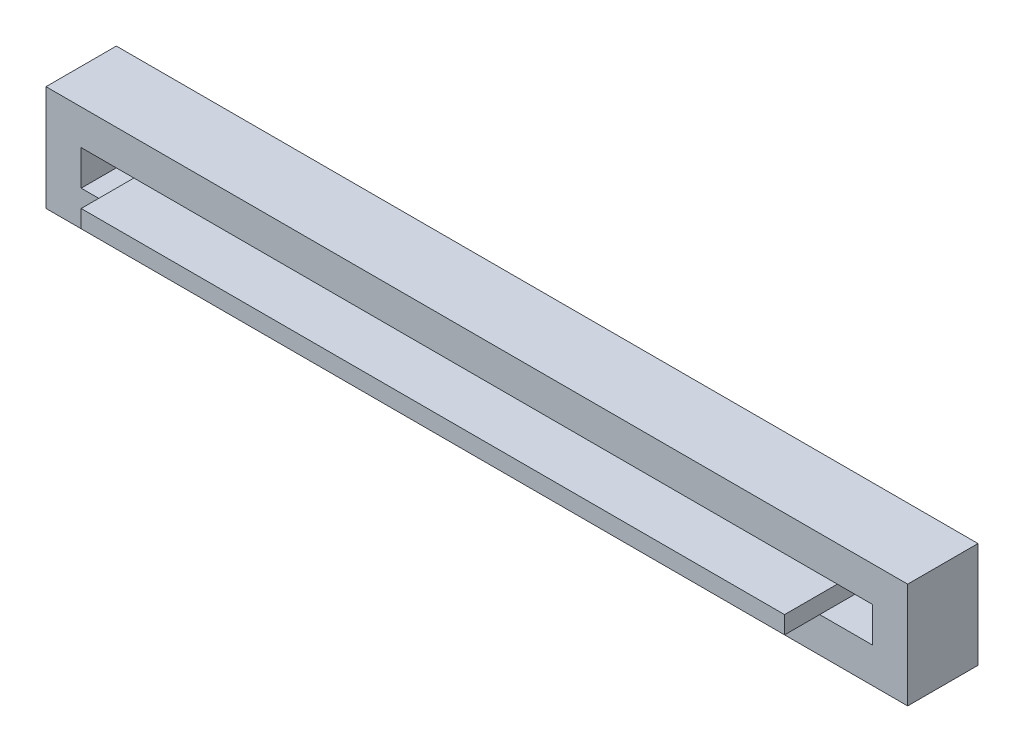
SolidWorks part; units mm, degrees
ref_plane "Front Plane" through (0, 0, 0) normal (0, 0, 1) x (1, 0, 0)
ref_plane "Top Plane" through (0, 0, 0) normal (0, 1, 0) x (1, 0, 0)
ref_plane "Right Plane" through (0, 0, 0) normal (1, 0, 0) x (0, 0, -1)
sketch "Sketch1" plane through (0, 0, 0) normal (0, 0, 1) x (1, 0, 0)
  line L1 (-22.5, 1) -> (22.5, 1)
  line L2 (-22.5, 1) -> (-22.5, -1)
  line L3 (-22.5, -1) -> (22.5, -1)
  line L4 (22.5, 1) -> (22.5, -1)
  line L5 (-22.5, 1) -> (22.5, -1) construction
  line L6 (-22.5, -1) -> (22.5, 1) construction
  line L7 (-24.5, 3) -> (24.5, 3)
  line L8 (-24.5, 3) -> (-24.5, -3)
  line L9 (-24.5, -3) -> (24.5, -3)
  line L10 (24.5, 3) -> (24.5, -3)
  line L11 (-24.5, 3) -> (24.5, -3) construction
  line L12 (-24.5, -3) -> (24.5, 3) construction
  point P0 (0, 0)
  point P6 (0, 0)
  dimension "D1" = 45
  dimension "D2" = 2
  dimension "D3" = 6
  dimension "D4" = 49
extrude "Boss-Extrude1" add sketch "Sketch1" along normal blind 2 contours L4 L1 L2 L3 region at (0, 0, 0)
extrude "Boss-Extrude2" add sketch "Sketch1<3>" along normal blind 4
sketch "Sketch1<3>" plane through (0, 0, 0) normal (0, 0, 1) x (1, 0, 0) same geometry as "Sketch1"
sketch "Sketch2" plane through (0, 0, 2) normal (0, 0, 1) x (1, 0, 0)
  line L1 (-20, 0.5) -> (20, 0.5)
  line L2 (-20, 0.5) -> (-20, -0.5)
  line L3 (-20, -0.5) -> (20, -0.5)
  line L4 (20, 0.5) -> (20, -0.5)
  line L5 (-20, 0.5) -> (20, -0.5) construction
  line L6 (-20, -0.5) -> (20, 0.5) construction
  point P0 (0, 0)
  dimension "D1" = 40
  dimension "D2" = 1
extrude "Boss-Extrude3" add sketch "Sketch2" along normal blind 4.5
